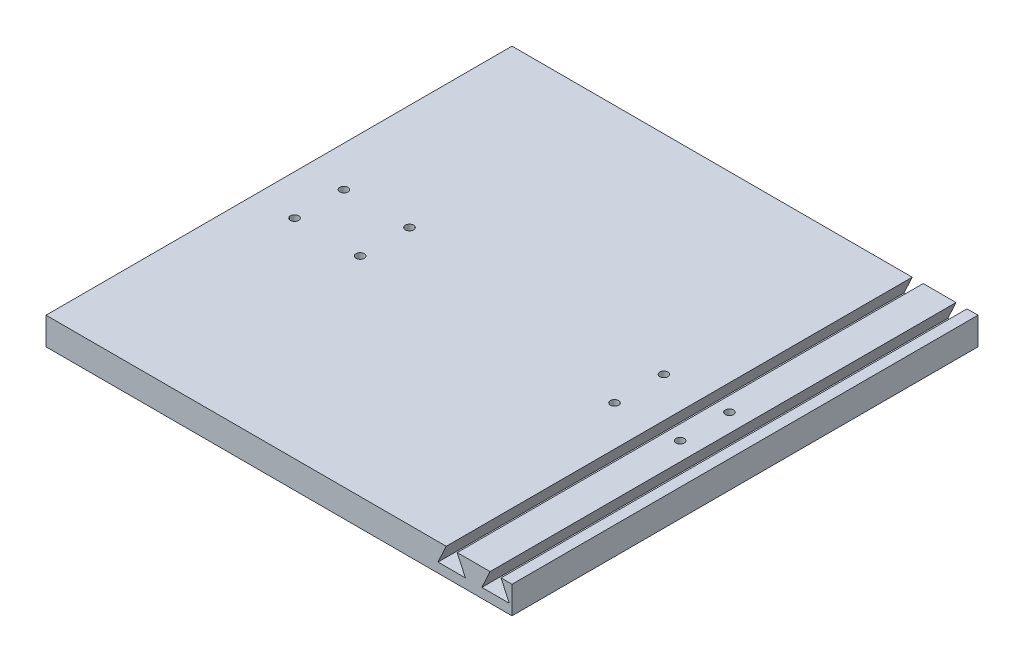
SolidWorks part; units mm, degrees
ref_plane "Front Plane" through (0, 0, 0) normal (0, 0, 1) x (1, 0, 0)
ref_plane "Top Plane" through (0, 0, 0) normal (0, 1, 0) x (1, 0, 0)
ref_plane "Right Plane" through (0, 0, 0) normal (1, 0, 0) x (0, 0, -1)
sketch "Sketch2" plane through (0, 0, 0) normal (0, 1, 0) x (1, 0, 0)
  line L1 (-85, -85) -> (85, -85)
  line L2 (-85, -85) -> (-85, 85)
  line L3 (-85, 85) -> (85, 85)
  line L4 (85, -85) -> (85, 85)
  line L5 (-85, -85) -> (85, 85) construction
  line L6 (-85, 85) -> (85, -85) construction
  point P0 (0, 0)
  dimension "D1" = 170
  dimension "D2" = 170
extrude "Boss-Extrude1" add sketch "Sketch2" along normal blind 10
sketch "Sketch4" plane through (0, 0, 0) normal (0, -1, 0) x (-1, 0, 0)
  circle A0 centre (-70.33, -9) radius 1.5
  circle A1 centre (-70.33, 9) radius 1.5
  circle A2 centre (70.33, 9) radius 1.5
  circle A3 centre (70.33, -9) radius 1.5
  circle A4 centre (46.4, 9) radius 1.5
  circle A5 centre (46.4, -9) radius 1.5
  circle A6 centre (-46.4, -9) radius 1.5
  circle A7 centre (-46.4, 9) radius 1.5
extrude "Cut-Extrude2" cut sketch "Sketch4" along normal through all and the other way through all
sketch "Sketch5" plane through (0, 0, -85) normal (0, 0, -1) x (-1, 0, 0)
  line L0 (-58, 3.5) -> (-61, 10)
  line L2 (-84, 3.5) -> (-74, 3.5)
  line L3 (-85, 10) -> (85, 10) construction
  line L4 (-81, 10) -> (-76.9988, 10)
  line L5 (-84, 3.5) -> (-81, 10)
  line L8 (-76.9988, 10) -> (-74, 3.5)
  line L11 (-58, 3.5) -> (-68, 3.5)
  line L12 (-65.0012, 10) -> (-68, 3.5)
  line L13 (-61, 10) -> (-65.0012, 10)
extrude "Cut-Extrude5" cut sketch "Sketch5" against normal blind 200
